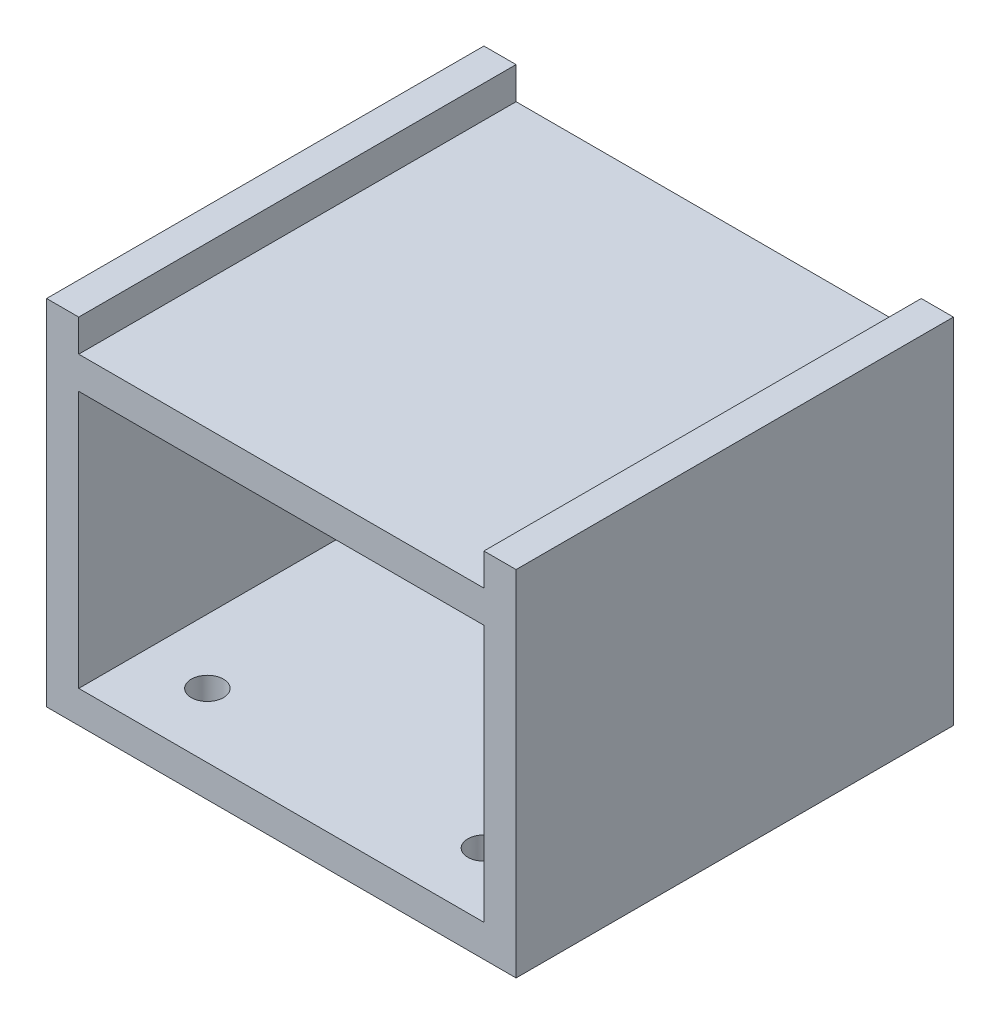
SolidWorks part; units mm, degrees
material "ABS"
ref_plane "Front Plane" through (0, 0, 0) normal (0, 0, 1) x (1, 0, 0)
ref_plane "Top Plane" through (0, 0, 0) normal (0, 1, 0) x (1, 0, 0)
ref_plane "Right Plane" through (0, 0, 0) normal (1, 0, 0) x (0, 0, -1)
sketch "Sketch1" plane through (0, 0, 0) normal (1, 0, 0) x (0, 0, -1)
  line L1 (-43.18, -31.75) -> (43.18, -31.75)
  line L2 (-43.18, -31.75) -> (-43.18, 31.75)
  line L3 (-43.18, 31.75) -> (43.18, 31.75)
  line L4 (43.18, -31.75) -> (43.18, 31.75)
  line L5 (-43.18, -31.75) -> (43.18, 31.75) construction
  line L6 (-43.18, 31.75) -> (43.18, -31.75) construction
  point P0 (0, 0)
  dimension "D1" = 86.36
  dimension "D2" = 63.5
extrude "Boss-Extrude1" add sketch "Sketch1" along normal blind 92.71
sketch "Sketch2" plane through (0, 31.75, 0) normal (0, 1, 0) x (1, 0, 0)
  line L0 (46.355, 43.18) -> (46.355, -43.18) construction
  line L1 (92.71, 43.18) -> (0, 43.18) construction
  line L2 (92.71, -43.18) -> (0, -43.18) construction
  line L3 (92.71, -43.18) -> (86.36, -43.18)
  line L4 (0, 43.18) -> (6.35, 43.18)
  line L5 (0, 43.18) -> (0, -43.18)
  line L6 (0, -43.18) -> (6.35, -43.18)
  line L7 (6.35, 43.18) -> (6.35, -43.18)
  line L8 (92.71, 43.18) -> (92.71, -43.18)
  line L9 (92.71, 43.18) -> (86.36, 43.18)
  line L10 (86.36, 43.18) -> (86.36, -43.18)
  dimension "D1" = 6.35
extrude "Boss-Extrude2" add sketch "Sketch2" along normal blind 6.35
sketch "Sketch4" plane through (0, 0, 0) normal (0, 0, 1) x (1, 0, 0)
  line L0 (6.35, 25.4) -> (6.35, -25.4)
  line L1 (6.35, -25.4) -> (86.36, -25.4)
  line L2 (86.36, -25.4) -> (86.36, 25.4)
  line L3 (86.36, 25.4) -> (86.36, 25.4)
  line L4 (86.36, 25.4) -> (86.36, 25.4)
  line L5 (86.36, 25.4) -> (6.35, 25.4)
  line L6 (6.35, 25.4) -> (6.35, 25.4)
  line L7 (6.35, 25.4) -> (6.35, 25.4)
  line L8 (0, 38.1) -> (0, -31.75)
  line L9 (0, -31.75) -> (92.71, -31.75)
  line L10 (92.71, -31.75) -> (92.71, 38.1)
  line L11 (92.71, 38.1) -> (86.36, 38.1)
  line L12 (86.36, 38.1) -> (86.36, 31.75)
  line L13 (86.36, 31.75) -> (6.35, 31.75)
  line L14 (6.35, 31.75) -> (6.35, 38.1)
  line L15 (6.35, 38.1) -> (0, 38.1)
  line L16 (0, 38.1) -> (0, -31.75) construction
  line L17 (0, -31.75) -> (92.71, -31.75) construction
  line L18 (92.71, -31.75) -> (92.71, 38.1) construction
  line L19 (92.71, 38.1) -> (86.36, 38.1) construction
  line L20 (86.36, 38.1) -> (86.36, 31.75) construction
  line L21 (86.36, 31.75) -> (6.35, 31.75) construction
  line L22 (6.35, 31.75) -> (6.35, 38.1) construction
  line L23 (6.35, 38.1) -> (0, 38.1) construction
  dimension "D1" = 0
  dimension "D2" = 6.35
extrude "Cut-Extrude2" cut sketch "Sketch4" against normal through all both and the other way through all
sketch "Sketch5" plane through (0, -25.4, 0) normal (0, 1, 0) x (1, 0, 0)
  line L0 (46.355, 43.18) -> (46.355, -43.18) construction
  line L1 (86.36, 43.18) -> (6.35, 43.18) construction
  line L2 (86.36, -43.18) -> (6.35, -43.18) construction
  line L3 (0, 0) -> (92.71, 0) construction
  line L4 (92.71, -43.18) -> (92.71, 43.18) construction
  line L6 (0, 43.18) -> (0, -43.18) construction
  circle A0 centre (19.05, 30.48) radius 3.175
  circle A1 centre (73.66, 30.48) radius 3.175
  circle A2 centre (73.66, -30.48) radius 3.175
  circle A3 centre (19.05, -30.48) radius 3.175
  point P15 (1.7921, 28.8086)
  dimension "D1" = 6.35
  dimension "D2" = 12.7
  dimension "D3" = 19.05
extrude "Cut-Extrude3" cut sketch "Sketch5" against normal through all
